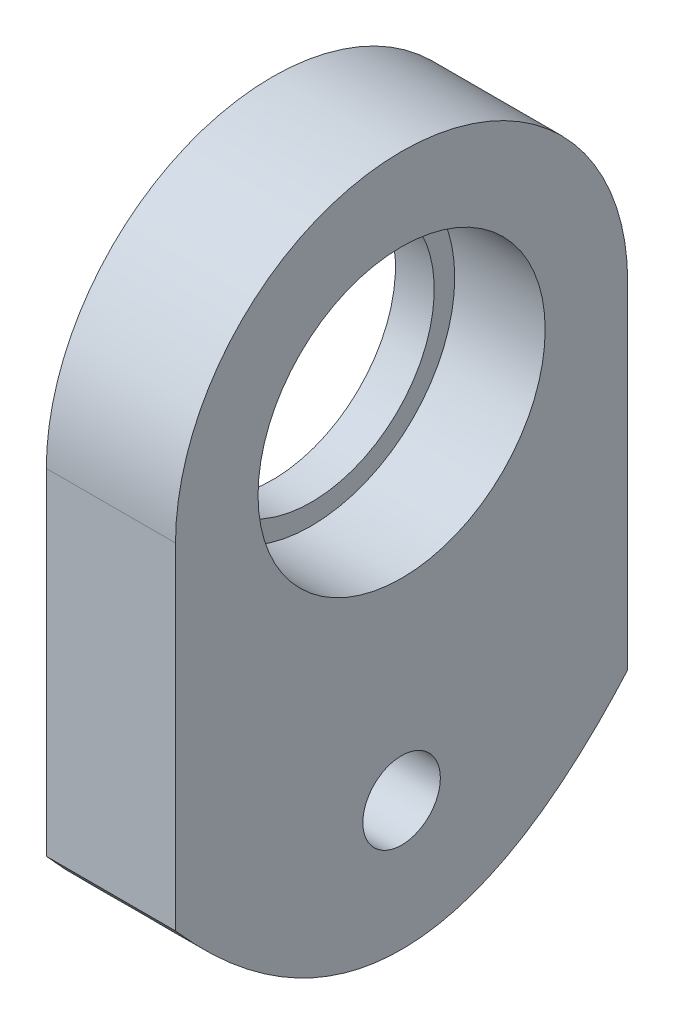
SolidWorks part; units mm, degrees
ref_plane "Alzado" through (0, 0, 0) normal (0, 0, 1) x (1, 0, 0)
ref_plane "Planta" through (0, 0, 0) normal (0, 1, 0) x (1, 0, 0)
ref_plane "Vista lateral" through (0, 0, 0) normal (1, 0, 0) x (0, 0, -1)
sketch "Croquis1" plane through (0, 0, 0) normal (1, 0, 0) x (0, 0, -1)
  line L3 (-3.5368, 13.8741) -> (-13.7837, -3.8741)
  line L4 (-10.247, -10) -> (10.247, -10)
  line L5 (13.7837, -3.8741) -> (3.5368, 13.8741)
  line L7 (17.5, 0) -> (17.5, -26)
  line L8 (-17.5, 0) -> (-17.5, -26)
  arc A10 (11.8234, -9.2308) -> (13.9058, -5.624) centre (0, 0) ccw
  arc A11 (2.0824, 14.8548) -> (-2.0824, 14.8548) centre (0, 0) ccw
  arc A13 (-13.7837, -3.8741) -> (-13.9058, -5.624) centre (-12.0517, -4.8741) ccw
  arc A14 (-10.247, -10) -> (-11.8234, -9.2308) centre (-10.247, -8) cw
  arc A15 (10.247, -10) -> (11.8234, -9.2308) centre (10.247, -8) ccw
  arc A16 (13.7837, -3.8741) -> (13.9058, -5.624) centre (12.0517, -4.8741) cw
  arc A17 (3.5368, 13.8741) -> (2.0824, 14.8548) centre (1.8047, 12.8741) ccw
  arc A18 (-3.5368, 13.8741) -> (-2.0824, 14.8548) centre (-1.8047, 12.8741) cw
  arc A19 (-14.3624, -4.3269) -> (-11.8234, -9.2308) centre (0, 0) ccw
  arc A20 (17.5, 0) -> (-17.5, 0) centre (0, 0) ccw
  circle A21 centre (0, -26) radius 26 construction
  circle A22 centre (0, -26) radius 2.5
  spline S0 degree 2 poles (-17.5, -26) (0, -46) (17.5, -26) knots 0 0 0 1 1 1
  dimension "D1" = 30
  dimension "D2" = 35
  dimension "D3" = 26
  dimension "D4" = 5
extrude "Saliente-Extruir2" add sketch "Croquis1" along normal blind 10 contours L8 S0 L7 A20 A19 A13 L3 A18 A11 A17 L5 A16 A10 A15 L4 A14 A22 region at (0, -13.039, 0)
ref_axis "Eje1" through (10, -26, 0) along (-1, 0, 0)
ref_axis "Eje2" through (10, 0, 0) along (-1, 0, 0)
sketch "Croquis2" plane through (0, 0, 0) normal (-1, 0, 0) x (0, 0, 1)
  line L0 (-11.0196, -1.4341) -> (-5.702, -9.5381)
  line L4 (6.7518, -8.8262) -> (11.1112, -0.169)
  line L7 (4.2678, 10.2603) -> (-5.4092, 9.7071)
  circle A0 centre (0, 0) radius 11.1125
  circle A1 centre (0, 0) radius 17.5
  arc M3 (13.9058, -5.624) -> (11.8234, -9.2308) centre (0, 0) cw
  arc M4 (11.8234, -9.2308) -> (10.247, -10) centre (10.247, -8) cw
  line M5 (10.247, -10) -> (-10.247, -10)
  arc M6 (-10.247, -10) -> (-11.8234, -9.2308) centre (-10.247, -8) cw
  arc M7 (-11.8234, -9.2308) -> (-13.9058, -5.624) centre (0, 0) cw
  arc M8 (-13.9058, -5.624) -> (-13.7837, -3.8741) centre (-12.0517, -4.8741) cw
  line M9 (-13.7837, -3.8741) -> (-3.5368, 13.8741)
  arc M10 (-3.5368, 13.8741) -> (-2.0824, 14.8548) centre (-1.8047, 12.8741) cw
  arc M11 (-2.0824, 14.8548) -> (2.0824, 14.8548) centre (0, 0) cw
  arc M12 (2.0824, 14.8548) -> (3.5368, 13.8741) centre (1.8047, 12.8741) cw
  line M13 (3.5368, 13.8741) -> (13.7837, -3.8741)
  arc M14 (13.7837, -3.8741) -> (13.9058, -5.624) centre (12.0517, -4.8741) cw
  arc M17 (17.5, 0) -> (-17.5, 0) centre (0, 0) ccw
  dimension "D1" = 22.225
extrude "Saliente-Extruir3" add sketch "Croquis2" against normal blind 10 contours A1 A0 M17 M13 M14 M3 M4 M5 M6 M7 M8 M9 M10 M11 M12 | A0 M9 M8 M7 M6 M5 | A0 M5 M4 M3 M14 M13 | A0 M13 M12 M11 M10 M9 region at (0, -6.2371, -10.8029) region at (0, 12.4742, 0) region at (0, -6.2371, 10.8029) region at (0, -17.005, 0)
sketch "Croquis3" plane through (0, 0, 0) normal (-1, 0, 0) x (0, 0, 1)
  line L0 (-11.0835, 0.8029) -> (-6.2371, 9.1971)
  line L1 (6.2371, 9.1971) -> (11.0835, 0.8029)
  line L2 (4.8464, -10) -> (-4.8464, -10)
  circle A0 centre (0, 0) radius 11.1125
  arc M2 (-6.2371, 9.1971) -> (6.2371, 9.1971) centre (0, 0) cw
  line M3 (6.2371, 9.1971) -> (11.0835, 0.8029)
  arc M4 (11.0835, 0.8029) -> (4.8464, -10) centre (0, 0) cw
  line M5 (4.8464, -10) -> (-4.8464, -10)
  arc M6 (-4.8464, -10) -> (-11.0835, 0.8029) centre (0, 0) cw
  line M7 (-11.0835, 0.8029) -> (-6.2371, 9.1971)
extrude "Cortar-Extruir1" cut sketch "Croquis3" against normal blind 10 contours A0 M7 | A0 M3 | A0 M5 | M2 M7 M6 M5 M4 M3 region at (0, 5.2235, -9.0473) region at (0, 0, 0) region at (0, -10.447, 0) region at (0, 5.2235, 9.0473)
sketch "Croquis4" plane through (0, 0, 0) normal (-1, 0, 0) x (0, 0, 1)
  circle A0 centre (0, 0) radius 11.1125
  circle A1 centre (0, 0) radius 9.525
  dimension "D1" = 19.05
extrude "Saliente-Extruir4" add sketch "Croquis4" against normal blind 3 contours A0 | A1
sketch "Croquis5" plane through (10, 0, 0) normal (1, 0, 0) x (0, 0, -1)
  circle A0 centre (0, -26) radius 3
  dimension "D1" = 6
extrude "Cortar-Extruir2" cut sketch "Croquis5" against normal blind 10
